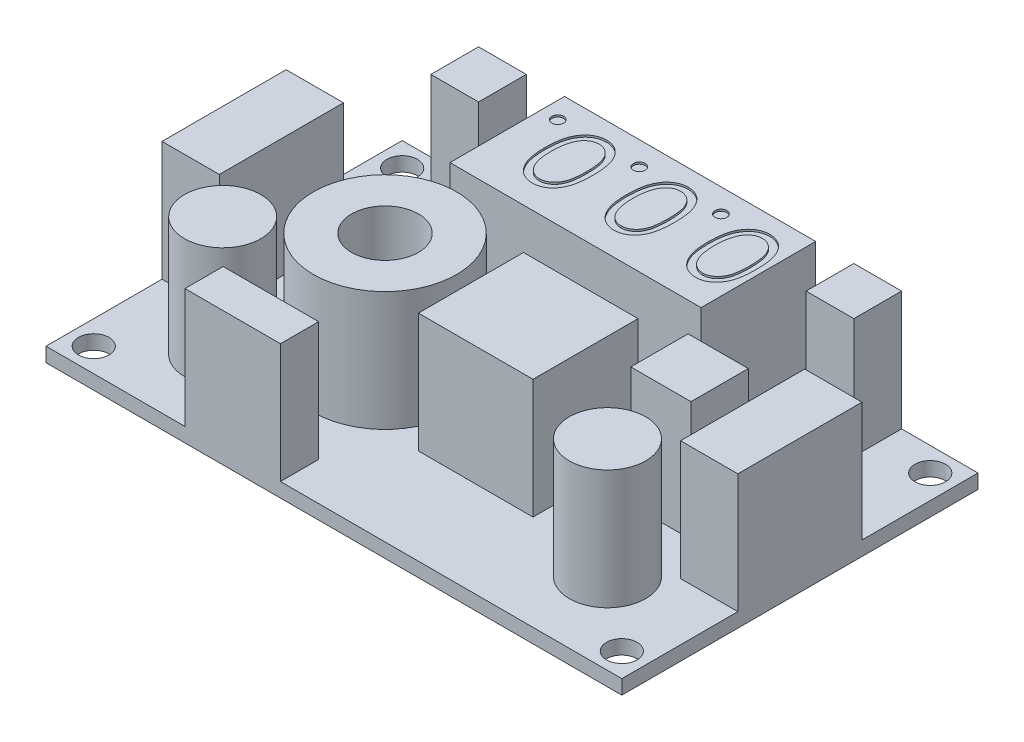
SolidWorks part; units mm, degrees
ref_plane "정면" through (0, 0, 0) normal (0, 0, 1) x (1, 0, 0)
ref_plane "윗면" through (0, 0, 0) normal (0, 1, 0) x (1, 0, 0)
ref_plane "우측면" through (0, 0, 0) normal (1, 0, 0) x (0, 0, -1)
sketch "스케치2" plane through (0, 0, 0) normal (0, 1, 0) x (1, 0, 0)
  line L1 (-30.15, 18.65) -> (30.15, 18.65)
  line L2 (-30.15, 18.65) -> (-30.15, -18.65)
  line L3 (-30.15, -18.65) -> (30.15, -18.65)
  line L4 (30.15, 18.65) -> (30.15, -18.65)
  line L5 (-30.15, 18.65) -> (30.15, -18.65) construction
  line L6 (-30.15, -18.65) -> (30.15, 18.65) construction
  point P0 (0, 0)
  dimension "D1" = 60.3
  dimension "D2" = 37.3
extrude "보스-돌출1" add sketch "스케치2" along normal blind 1.5
sketch "스케치3" plane through (0, 1.5, 0) normal (0, 1, 0) x (1, 0, 0)
  line L0 (-30.15, 18.65) -> (-30.15, -18.65) construction
  line L1 (-30.15, 6.5) -> (-24.15, 6.5)
  line L2 (-30.15, 6.5) -> (-30.15, -6.5)
  line L3 (-30.15, -6.5) -> (-24.15, -6.5)
  line L4 (-24.15, 6.5) -> (-24.15, -6.5)
  line L5 (30.15, -18.65) -> (30.15, 18.65) construction
  line L6 (30.15, 6.5) -> (24.15, 6.5)
  line L7 (30.15, 6.5) -> (30.15, -6.5)
  line L8 (30.15, -6.5) -> (24.15, -6.5)
  line L9 (24.15, 6.5) -> (24.15, -6.5)
  line L10 (-30.15, -18.65) -> (30.15, -18.65) construction
  line L11 (-15.6008, -18.65) -> (-5.6008, -18.65)
  line L12 (-15.6008, -18.65) -> (-15.6008, -14.65)
  line L13 (-15.6008, -14.65) -> (-5.6008, -14.65)
  line L14 (-5.6008, -18.65) -> (-5.6008, -14.65)
  line L15 (30.15, 18.65) -> (-30.15, 18.65) construction
  line L16 (-1.15, 2.35) -> (10.85, 2.35)
  line L17 (-1.15, 2.35) -> (-1.15, -8.65)
  line L18 (-1.15, -8.65) -> (10.85, -8.65)
  line L19 (10.85, 2.35) -> (10.85, -8.65)
  line L20 (-1.15, 2.35) -> (10.85, -8.65) construction
  line L21 (-1.15, -8.65) -> (10.85, 2.35) construction
  line L22 (-22.15, 18.65) -> (-17.15, 18.65)
  line L23 (-22.15, 18.65) -> (-22.15, 13.65)
  line L24 (-22.15, 13.65) -> (-17.15, 13.65)
  line L25 (-17.15, 18.65) -> (-17.15, 13.65)
  line L27 (17.15, 18.65) -> (22.15, 18.65)
  line L28 (17.15, 18.65) -> (17.15, 13.65)
  line L29 (17.15, 13.65) -> (22.15, 13.65)
  line L30 (22.15, 18.65) -> (22.15, 13.65)
  line L31 (-13.15, 18.65) -> (13.15, 18.65)
  line L32 (-13.15, 18.65) -> (-13.15, 6.65)
  line L33 (-13.15, 6.65) -> (13.15, 6.65)
  line L34 (13.15, 18.65) -> (13.15, 6.65)
  line L35 (14.85, 3.5915) -> (21.15, 3.5915)
  line L36 (14.85, 3.5915) -> (14.85, -2.4085)
  line L37 (14.85, -2.4085) -> (21.15, -2.4085)
  line L38 (21.15, 3.5915) -> (21.15, -2.4085)
  circle A0 centre (-20.15, -10.15) radius 4
  circle A1 centre (20.15, -10.15) radius 4
  circle A2 centre (-10.15, -3.15) radius 7.5
  circle A3 centre (-10.15, -3.15) radius 3.5
  point P12 (-30.15, 0)
  point P13 (-30.15, 0)
  point P27 (4.85, -3.15)
  dimension "D3" = 10
  dimension "D5" = 8
  dimension "D7" = 10
  dimension "D8" = 8.5
  dimension "D9" = 10
  dimension "D10" = 15
  dimension "D11" = 7
  dimension "D12" = 7
  dimension "D13" = 10
  dimension "D16" = 9
  dimension "D1" = 6
  dimension "D2" = 13
  dimension "D4" = 4
  dimension "D6" = 8.5
  dimension "D14" = 12
  dimension "D15" = 11
  dimension "D17" = 5
  dimension "D18" = 5
  dimension "D19" = 5
  dimension "D20" = 8
  dimension "D21" = 8
  dimension "D22" = 4
  dimension "D23" = 4
  dimension "D24" = 12
  dimension "D25" = 4
  dimension "D26" = 3
  dimension "D27" = 6
extrude "보스-돌출2" add sketch "스케치3" along normal blind 12.5
extrude "보스-돌출3" add sketch "스케치3<2>" along normal blind 8
sketch "스케치3<2>" plane through (0, 1.5, 0) normal (0, 1, 0) x (1, 0, 0) same geometry as "스케치3"
sketch "스케치5" plane through (0, 14, 0) normal (0, 1, 0) x (1, 0, 0)
  line L0 (-13.15, 16.7069) -> (13.15, 16.7069) construction
  line L1 (-13.15, 18.65) -> (-13.15, 6.65) construction
  line L2 (13.15, 6.65) -> (13.15, 18.65) construction
  text T0 "0.0.0." font "Century Gothic" height in points 28
extrude "컷-돌출1" cut sketch "스케치5" against normal blind 0.2
sketch "스케치6" plane through (0, 1.5, 0) normal (0, 1, 0) x (1, 0, 0)
  line L0 (-22.15, 18.65) -> (-30.15, 18.65) construction
  line L1 (-27.65, -16.15) -> (27.65, -16.15) construction
  line L2 (-27.65, -16.15) -> (-27.65, 16.15) construction
  line L3 (-27.65, 16.15) -> (27.65, 16.15) construction
  line L4 (27.65, -16.15) -> (27.65, 16.15) construction
  line L5 (-30.15, 18.65) -> (-30.15, 6.5) construction
  line L6 (-5.6008, -18.65) -> (30.15, -18.65) construction
  line L7 (30.15, -18.65) -> (30.15, -6.5) construction
  circle A0 centre (-27.65, 16.15) radius 1.6
  circle A1 centre (27.65, 16.15) radius 1.6
  circle A2 centre (27.65, -16.15) radius 1.6
  circle A3 centre (-27.65, -16.15) radius 1.6
  dimension "D5" = 3.2
  dimension "D1" = 2.5
  dimension "D2" = 2.5
  dimension "D3" = 2.5
  dimension "D4" = 2.5
extrude "컷-돌출2" cut sketch "스케치6" against normal through all
